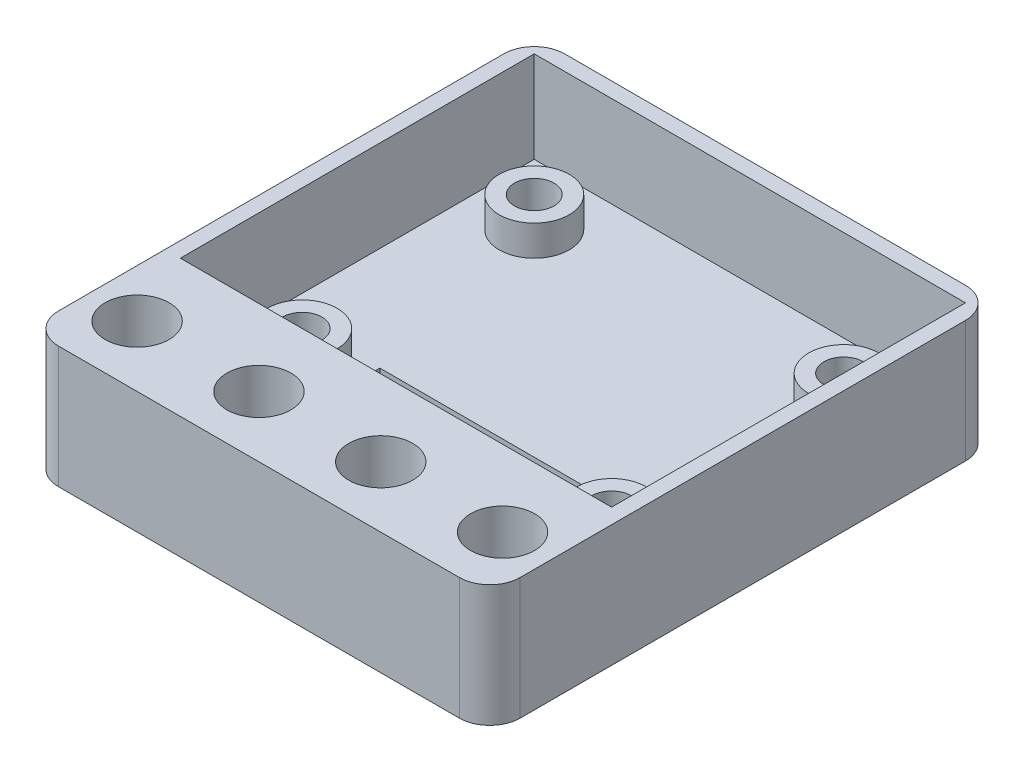
SolidWorks part; units mm, degrees
ref_plane "Front Plane" through (0, 0, 0) normal (0, 0, 1) x (1, 0, 0)
ref_plane "Top Plane" through (0, 0, 0) normal (0, 1, 0) x (1, 0, 0)
ref_plane "Right Plane" through (0, 0, 0) normal (1, 0, 0) x (0, 0, -1)
sketch "Sketch1" plane through (0, 0, 0) normal (0, 1, 0) x (1, 0, 0)
  line L0 (14.16, 11.62) -> (-14.16, 11.62)
  line L5 (15.16, 12.62) -> (-15.16, 12.62)
  line L6 (7.36, -9.92) -> (-7.36, -9.92)
  line L7 (10.16, -7.62) -> (-10.16, -7.62) construction
  line L8 (10.16, -7.62) -> (10.16, 7.62) construction
  line L9 (10.16, 7.62) -> (-10.16, 7.62) construction
  line L10 (-10.16, -7.62) -> (-10.16, 7.62) construction
  line L11 (0, 7.62) -> (0, -7.62) construction
  line L12 (10.16, 0) -> (-10.16, 0) construction
  line L13 (-14.16, -11.62) -> (-14.16, 11.62)
  line L14 (14.16, -11.62) -> (-14.16, -11.62)
  line L15 (14.16, -11.62) -> (14.16, 11.62)
  line L16 (7.36, -9.92) -> (7.36, -5.32)
  line L17 (7.36, -5.32) -> (-7.36, -5.32)
  line L18 (-7.36, -9.92) -> (-7.36, -5.32)
  line L19 (0, -5.32) -> (0, -9.92) construction
  line L20 (7.36, -7.62) -> (-7.36, -7.62) construction
  line L21 (-15.16, -12.62) -> (-15.16, 12.62)
  line L22 (15.16, -12.62) -> (-15.16, -12.62) construction
  line L23 (15.16, -12.62) -> (15.16, 12.62)
  line L24 (-15.16, -12.62) -> (-15.16, -20.62)
  line L25 (-15.16, -20.62) -> (15.16, -20.62)
  line L26 (15.16, -20.62) -> (15.16, -12.62)
  line L27 (-12, -16.62) -> (12, -16.62) construction
  line L28 (0, 0) -> (0, 50000) construction
  circle A0 centre (-10.16, 7.62) radius 1.3
  circle A1 centre (10.16, 7.62) radius 1.3
  circle A2 centre (10.16, -7.62) radius 1.3
  circle A3 centre (-10.16, -7.62) radius 1.3
  circle A4 centre (-10.16, 7.62) radius 2.3
  circle A5 centre (-10.16, -7.62) radius 2.3
  circle A6 centre (10.16, 7.62) radius 2.3
  circle A7 centre (10.16, -7.62) radius 2.3
  circle A8 centre (-12, -16.62) radius 2.1
  circle A9 centre (-4, -16.62) radius 2.1
  circle A10 centre (4, -16.62) radius 2.1
  circle A11 centre (12, -16.62) radius 2.1
  point P0 (0, 0)
  point P4 (0, 0)
  point P40 (0, -16.62)
  dimension "D2" = 2.6
  dimension "D6" = 2.8
  dimension "D11" = 4.2
  dimension "D1" = 4
  dimension "D3" = 15.24
  dimension "D4" = 20.32
  dimension "D8" = 8
  dimension "D9" = 4
  dimension "D10" = 4
  dimension "D12" = 8
  dimension "D5" = 1
  dimension "D7" = 1
extrude "Boss-Extrude1" add sketch "Sketch1" along normal blind 2 contours L14 L15 L0 L13 A7 A6 A5 A4 L6 L18 L17 L16 region at (0, 0, -0.9847)
extrude "Boss-Extrude2" add sketch "Sketch1<3>" along normal blind 4 contours A5 A3 | A7 A2 | A6 A1 | A4 A0 region at (-12.3949, 0, -7.62) region at (-12.3949, 0, 7.62) region at (7.9251, 0, -7.62) region at (7.9251, 0, 7.62)
sketch "Sketch1<3>" plane through (0, 0, 0) normal (0, 1, 0) x (1, 0, 0) same geometry as "Sketch1"
extrude "Boss-Extrude3" add sketch "Sketch1<4>" along normal blind 8 contours L22 L23 L5 L21 L15 L14 L13 L0 region at (14.7101, 0, 0)
sketch "Sketch1<4>" plane through (0, 0, 0) normal (0, 1, 0) x (1, 0, 0) same geometry as "Sketch1"
fillet "Fillet2" radius 2 4 edges at (15.16, 4, 20.62) (15.16, 4, -12.62) (-15.16, 4, -12.62) (-15.16, 4, 20.62)
